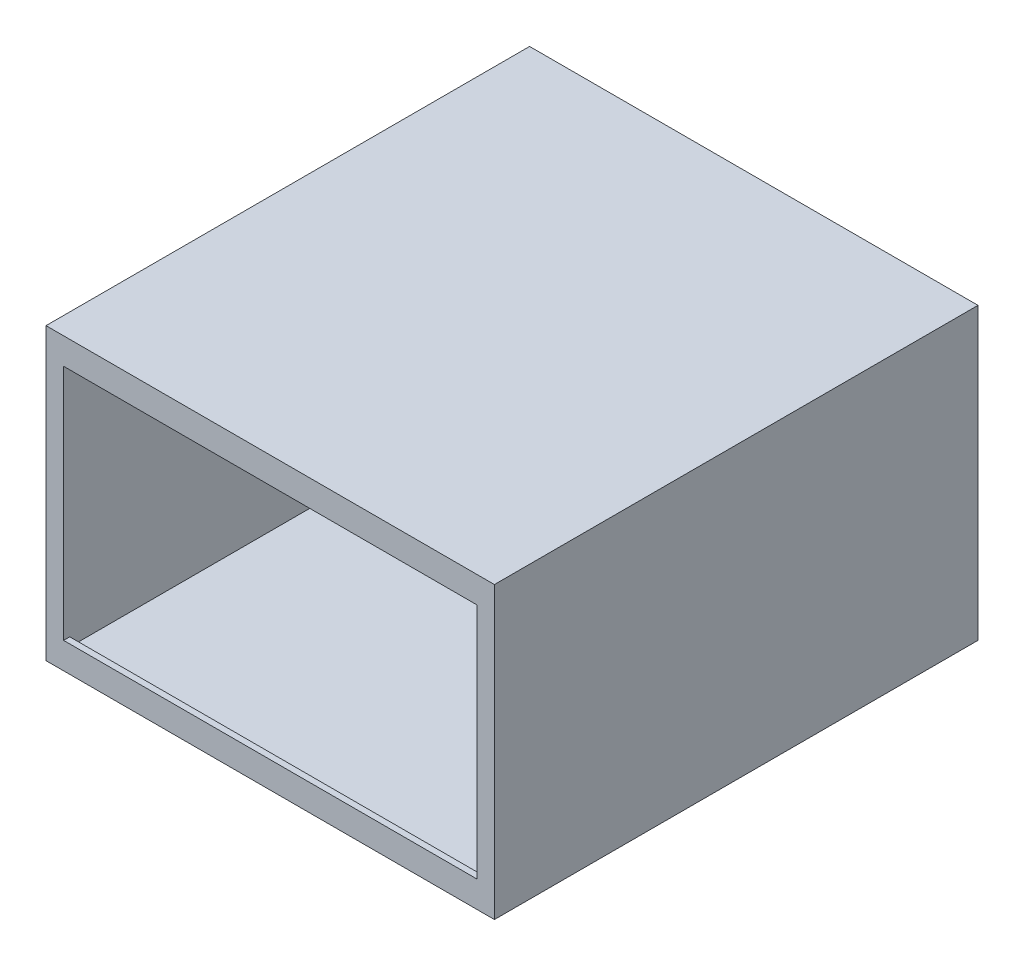
SolidWorks part; units mm, degrees
ref_plane "Front Plane" through (0, 0, 0) normal (0, 0, 1) x (1, 0, 0)
ref_plane "Top Plane" through (0, 0, 0) normal (0, 1, 0) x (1, 0, 0)
ref_plane "Right Plane" through (0, 0, 0) normal (1, 0, 0) x (0, 0, -1)
sketch "Sketch1" plane through (0, 0, 0) normal (0, 0, 1) x (1, 0, 0)
  line L1 (-23.5, 14.5) -> (23.5, 14.5)
  line L2 (-23.5, 14.5) -> (-23.5, -14.5)
  line L3 (-23.5, -14.5) -> (23.5, -14.5)
  line L4 (23.5, 14.5) -> (23.5, -14.5)
  line L5 (-25.5, 16.5) -> (25.5, 16.5)
  line L6 (-25.5, 16.5) -> (-25.5, -16.5)
  line L7 (-25.5, -16.5) -> (25.5, -16.5)
  line L8 (25.5, 16.5) -> (25.5, -16.5)
  circle A0 centre (0, 0) radius 4.5
  point P8 (-23.5, 0)
  point P9 (0, 16.5)
  point P10 (-25.5, 0)
  point P11 (0, 14.5)
  dimension "D1" = 47
  dimension "D2" = 29
  dimension "D3" = 2
  dimension "D4" = 2
extrude "Boss-Extrude1" add sketch "Sketch1" along normal blind 50 contours L8 L5 L6 L7 L1 L4 L3 L2 region at (0, 15.8925, 0)
extrude "Boss-Extrude2" add sketch "Sketch1<3>" against normal blind 5 contours L4 L1 L2 L3 A0 | L8 L5 L6 L7 L1 L4 L3 L2 region at (0, 13.9477, 0) region at (0, 15.8925, 0)
sketch "Sketch1<3>" plane through (0, 0, 0) normal (0, 0, 1) x (1, 0, 0) same geometry as "Sketch1"
sketch "Sketch2" plane through (0, 0, 50) normal (0, 0, 1) x (1, 0, 0)
  line L0 (25.5, 16.5) -> (25.5, -16.5) construction
  line L1 (-25.5, 16.5) -> (25.5, 16.5)
  line L2 (-25.5, 16.5) -> (-25.5, 13.5)
  line L3 (-25.5, 13.5) -> (25.5, 13.5)
  line L4 (25.5, 16.5) -> (25.5, 13.5)
  line L6 (25.5, -16.5) -> (-25.5, -16.5)
  line L7 (25.5, -16.5) -> (25.5, -13.5)
  line L8 (25.5, -13.5) -> (-25.5, -13.5)
  line L9 (-25.5, -16.5) -> (-25.5, -13.5)
  line L10 (-25.5, 16.5) -> (-25.5, -16.5) construction
  dimension "D1" = 3
  dimension "D2" = 3
  dimension "D3" = 51
extrude "Boss-Extrude3" add sketch "Sketch2" against normal blind 0.7
